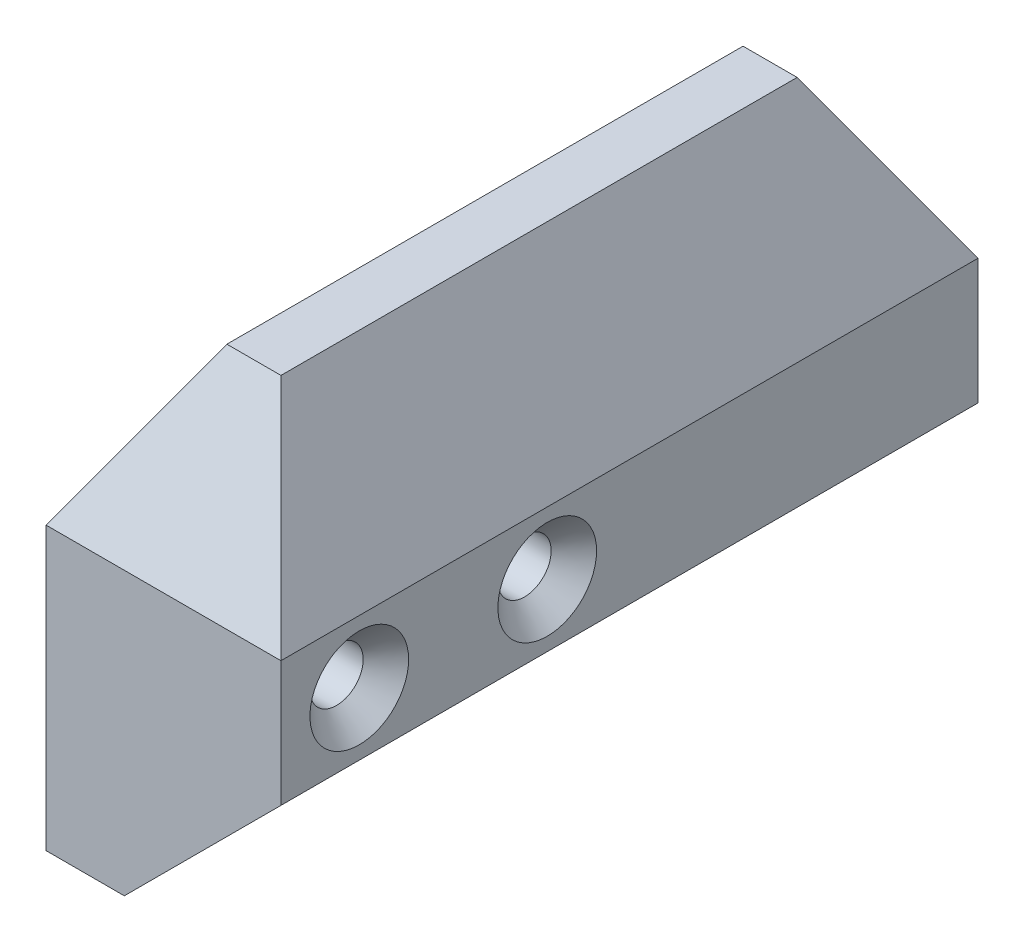
SolidWorks part; units mm, degrees
ref_plane "Plan de face" through (0, 0, 0) normal (0, 0, 1) x (1, 0, 0)
ref_plane "Plan de dessus" through (0, 0, 0) normal (0, 1, 0) x (1, 0, 0)
ref_plane "Plan de droite" through (0, 0, 0) normal (1, 0, 0) x (0, 0, -1)
sketch "Esquisse1" plane through (0, 0, 0) normal (0, 0, 1) x (1, 0, 0)
  line L0 (0, 8) -> (5.7735, 18)
  line L1 (0, 0) -> (15, 0)
  line L2 (0, 0) -> (0, 8)
  line L3 (5.7735, 18) -> (9.2265, 18)
  line L4 (15, 0) -> (15, 8)
  line L5 (9.2265, 18) -> (15, 8)
  dimension "D1" = 15
  dimension "D2" = 8
  dimension "D3" = 150
  dimension "D4" = 10
extrude "Boss.-Extru.1" add sketch "Esquisse1" along normal blind 44.5
ref_plane "Plan1" through (0, 21.2691, 36.8391) normal (0, 0.5, 0.866) x (-1, 0, 0)
ref_axis "Axe1" through (21.665, 18, 38.7265) along (-1, 0, 0)
sketch "Esquisse2" plane through (0, 21.2691, 36.8391) normal (0, 0.5, 0.866) x (-1, 0, 0)
  line L1 (0, 15.3218) -> (-15, 15.3218)
  line L2 (0, 15.3218) -> (0, 3.7748)
  line L3 (0, 3.7748) -> (-15, 3.7748)
  line L4 (-15, 15.3218) -> (-15, 3.7748)
  line L5 (-21.665, 3.7748) -> (-2.6455, 3.7748) construction
extrude "Enlèv. mat.-Extru.1" cut sketch "Esquisse2" along normal through all
ref_plane "Plan3" through (0, 2, -3.4641) normal (0, 0.5, -0.866) x (-1, 0, 0)
ref_axis "Axe2" through (9.2265, 18, 5.7735) along (-1, 0, 0)
sketch "Esquisse4" plane through (0, 2, -3.4641) normal (0, 0.5, -0.866) x (-1, 0, 0)
  line L0 (-9.2265, 18.4752) -> (-5.7735, 18.4752) construction
  line L1 (-15, 6.9282) -> (0, 6.9282)
  line L2 (-15, 6.9282) -> (-15, 18.4752)
  line L3 (-15, 18.4752) -> (0, 18.4752)
  line L4 (0, 6.9282) -> (0, 18.4752)
extrude "Enlèv. mat.-Extru.3" cut sketch "Esquisse4" along normal through all
sketch "Esquisse5" plane through (0, 0, 0) normal (0, 0, 1) x (1, 0, 0)
  line L0 (0, -10) -> (5, -10)
  line L1 (0, 0) -> (15, 0)
  line L2 (0, 0) -> (0, -10)
  line L3 (5, -10) -> (15, 0)
  line L4 (15, 0) -> (15, 8) construction
  dimension "D1" = 135
  dimension "D2" = 5
extrude "Boss.-Extru.4" add sketch "Esquisse5" along normal up to surface (44.5 mm away) up to face at (7.5, 4, 44.5)
hole_wizard "Fraisage pour vis à tête fraisée M31" positions "Esquisse7" profile "Esquisse6" countersink size "M3" standard "Ansi Metric" end condition through all
sketch "Esquisse7" plane through (15, 0, 0) normal (1, 0, 0) x (0, 0, -1)
  line L0 (-44.5, 0) -> (-44.5, 8) construction
  point P0 (-39.5, 4)
  point P13 (-44.5, 4)
  dimension "D1" = 5
sketch "Esquisse6" plane through (15, 4, 39.5) normal (0, 1, 0) x (0, 0, -1)
  line L0 (0, 0) -> (0, 15)
  line L1 (0, 15) -> (1.7, 15)
  line L2 (1.7, 15) -> (1.7, 1.45)
  line L3 (1.7, 1.45) -> (3.15, 0)
  line L5 (3.15, 0) -> (0, 0)
  line L6 (-1.7, 1.45) -> (-3.15, 0) construction
  line L11 (0, -6.35) -> (0, 107.95) construction
  dimension "Diamètre du perçage jusqu'au prochain" = 3.4
  dimension "Profondeur du perçage jusqu'au prochain" = 15
  dimension "Diamètre du fraisage entrant" = 6.3
  dimension "Angle du fraisage entrant" = 90
pattern_linear "Répétition linéaire1" count 2 spacing 12 along (0, 0, -1) of "Fraisage pour vis à tête fraisée M31"
